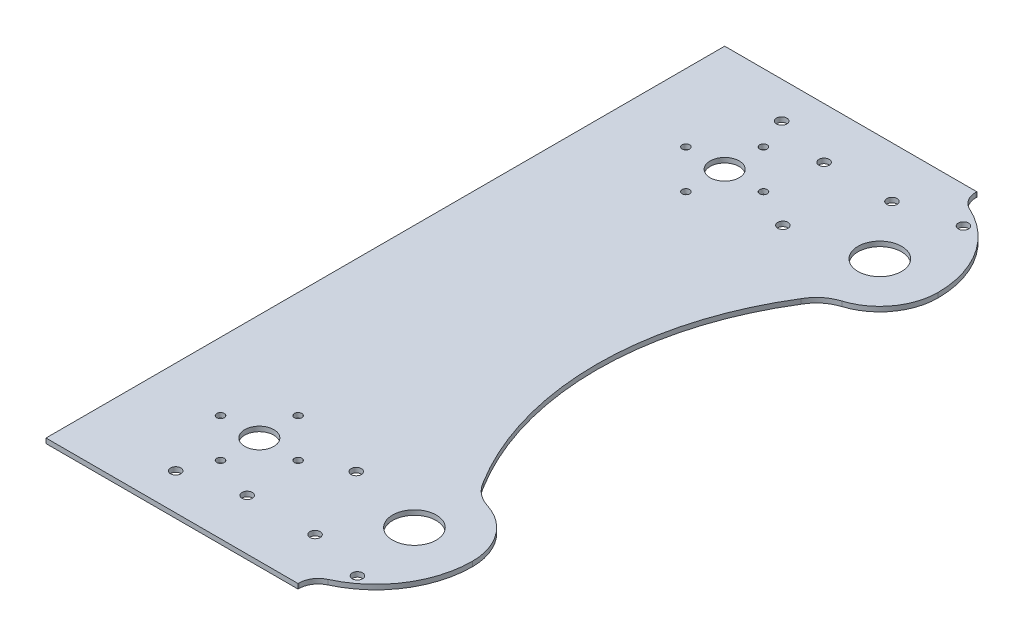
SolidWorks part; units mm, degrees
material "6061-T6 (SS)"
ref_plane "Front Plane" through (0, 0, 0) normal (0, 0, 1) x (1, 0, 0)
ref_plane "Top Plane" through (0, 0, 0) normal (0, 1, 0) x (1, 0, 0)
ref_plane "Right Plane" through (0, 0, 0) normal (1, 0, 0) x (0, 0, -1)
sketch "Sketch1" plane through (0, 0, 0) normal (0, 1, 0) x (1, 0, 0)
  line L1 (82.55, -222.25) -> (-82.55, -222.25)
  line L2 (82.55, -222.25) -> (82.55, 222.25)
  line L3 (82.55, 222.25) -> (-82.55, 222.25)
  line L4 (-82.55, -222.25) -> (-82.55, 222.25)
  line L5 (82.55, -222.25) -> (-82.55, 222.25) construction
  line L6 (82.55, 222.25) -> (-82.55, -222.25) construction
  point P0 (0, 0)
  dimension "D1" = 165.1
  dimension "D2" = 444.5
extrude "Boss-Extrude1" add sketch "Sketch1" along normal blind 3.175
sketch "Sketch3" plane through (0, 3.175, 0) normal (0, 1, 0) x (1, 0, 0)
  arc A0 (-3.175, -152.4) -> (-22.225, -152.4) centre (-12.7, -152.4) ccw construction
  arc A1 (-22.225, -152.4) -> (-3.175, -152.4) centre (-12.7, -152.4) ccw construction
  arc A2 (-3.175, -152.4) -> (-22.225, -152.4) centre (-12.7, -152.4) ccw
  arc A3 (-22.225, -152.4) -> (-3.175, -152.4) centre (-12.7, -152.4) ccw
  arc A4 (-3.175, 152.4) -> (-22.225, 152.4) centre (-12.7, 152.4) ccw construction
  arc A5 (-22.225, 152.4) -> (-3.175, 152.4) centre (-12.7, 152.4) ccw construction
  arc A6 (-3.175, 152.4) -> (-22.225, 152.4) centre (-12.7, 152.4) ccw
  arc A7 (-22.225, 152.4) -> (-3.175, 152.4) centre (-12.7, 152.4) ccw
extrude "Cut-Extrude2" cut sketch "Sketch3" against normal through all
hole_wizard "#10 (0.1935) Diameter Hole1" positions "Sketch4" profile "Sketch5" hole size "#10" standard "ANSI Inch" end condition through all
sketch "Sketch4" plane through (0, 3.175, 0) normal (0, 1, 0) x (1, 0, 0)
  arc A0 (-10.6807, -127) -> (-14.7193, -127) centre (-12.7, -127) ccw construction
  arc A1 (-14.7193, -127) -> (-10.6807, -127) centre (-12.7, -127) ccw construction
  arc A2 (-36.0807, -152.4) -> (-40.1193, -152.4) centre (-38.1, -152.4) ccw construction
  arc A3 (-40.1193, -152.4) -> (-36.0807, -152.4) centre (-38.1, -152.4) ccw construction
  arc A4 (-10.6807, -177.8) -> (-14.7193, -177.8) centre (-12.7, -177.8) ccw construction
  arc A5 (-14.7193, -177.8) -> (-10.6807, -177.8) centre (-12.7, -177.8) ccw construction
  arc A6 (14.7193, -152.4) -> (10.6807, -152.4) centre (12.7, -152.4) ccw construction
  arc A7 (10.6807, -152.4) -> (14.7193, -152.4) centre (12.7, -152.4) ccw construction
  arc A8 (-10.6807, -127) -> (-14.7193, -127) centre (-12.7, -127) ccw construction
  arc A9 (-14.7193, -127) -> (-10.6807, -127) centre (-12.7, -127) ccw construction
  arc A10 (-36.0807, -152.4) -> (-40.1193, -152.4) centre (-38.1, -152.4) ccw construction
  arc A11 (-40.1193, -152.4) -> (-36.0807, -152.4) centre (-38.1, -152.4) ccw construction
  arc A12 (-10.6807, -177.8) -> (-14.7193, -177.8) centre (-12.7, -177.8) ccw construction
  arc A13 (-14.7193, -177.8) -> (-10.6807, -177.8) centre (-12.7, -177.8) ccw construction
  arc A14 (14.7193, -152.4) -> (10.6807, -152.4) centre (12.7, -152.4) ccw construction
  arc A15 (10.6807, -152.4) -> (14.7193, -152.4) centre (12.7, -152.4) ccw construction
  arc A16 (14.7193, 152.4) -> (10.6807, 152.4) centre (12.7, 152.4) ccw construction
  arc A17 (10.6807, 152.4) -> (14.7193, 152.4) centre (12.7, 152.4) ccw construction
  arc A18 (-10.6807, 177.8) -> (-14.7193, 177.8) centre (-12.7, 177.8) ccw construction
  arc A19 (-14.7193, 177.8) -> (-10.6807, 177.8) centre (-12.7, 177.8) ccw construction
  arc A20 (-36.0807, 152.4) -> (-40.1193, 152.4) centre (-38.1, 152.4) ccw construction
  arc A21 (-40.1193, 152.4) -> (-36.0807, 152.4) centre (-38.1, 152.4) ccw construction
  arc A22 (-10.6807, 127) -> (-14.7193, 127) centre (-12.7, 127) ccw construction
  arc A23 (-14.7193, 127) -> (-10.6807, 127) centre (-12.7, 127) ccw construction
  arc A24 (14.7193, 152.4) -> (10.6807, 152.4) centre (12.7, 152.4) ccw
  arc A25 (10.6807, 152.4) -> (14.7193, 152.4) centre (12.7, 152.4) ccw
  arc A26 (-10.6807, 177.8) -> (-14.7193, 177.8) centre (-12.7, 177.8) ccw
  arc A27 (-14.7193, 177.8) -> (-10.6807, 177.8) centre (-12.7, 177.8) ccw
  arc A28 (-36.0807, 152.4) -> (-40.1193, 152.4) centre (-38.1, 152.4) ccw
  arc A29 (-40.1193, 152.4) -> (-36.0807, 152.4) centre (-38.1, 152.4) ccw
  arc A30 (-10.6807, 127) -> (-14.7193, 127) centre (-12.7, 127) ccw
  arc A31 (-14.7193, 127) -> (-10.6807, 127) centre (-12.7, 127) ccw
  point P0 (-12.7, -177.8)
  point P2 (-38.1, -152.4)
  point P4 (-12.7, -127)
  point P6 (12.7, -152.4)
  point P44 (-12.7, 177.8)
  point P50 (-38.1, 152.4)
  point P56 (-12.7, 127)
  point P68 (12.7, 152.4)
sketch "Sketch5" plane through (-12.7, 3.175, 177.8) normal (1, 0, 0) x (0, 0, 1)
  line L0 (0, 0) -> (0, 3.175)
  line L1 (0, 3.175) -> (2.4574, 3.175)
  line L2 (2.4574, 3.175) -> (2.4574, 0)
  line L5 (2.4574, 0) -> (0, 0)
  line L11 (0, -6.35) -> (0, 107.95) construction
  dimension "Thru Hole Dia." = 4.9149
  dimension "Thru Hole Depth" = 3.175
sketch "Sketch6" plane through (0, 3.175, 0) normal (0, 1, 0) x (1, 0, 0)
  line L0 (-12.7, -114.3) -> (-12.7, 114.3) construction
  line L1 (88.9, -152.4) -> (-12.7, -152.4) construction
  line L2 (88.9, 152.4) -> (-12.7, 152.4) construction
  line L3 (88.9, 152.4) -> (82.55, 152.4) construction
  line L4 (82.55, -222.25) -> (82.55, 222.25) construction
  circle A0 centre (-12.7, -152.4) radius 38.1 construction
  circle A1 centre (-12.7, 152.4) radius 38.1 construction
  circle A2 centre (88.9, -152.4) radius 38.1 construction
  circle A3 centre (88.9, 152.4) radius 38.1 construction
  dimension "D1" = 76.2
  dimension "D2" = 228.6
  dimension "D3" = 101.6
  dimension "D4" = 6.35
sketch "Sketch9" plane through (0, 0, 0) normal (0, 1, 0) x (1, 0, 0)
  line L0 (82.55, 222.25) -> (82.55, 212.9751)
  line L1 (82.55, -222.25) -> (82.55, 222.25) construction
  line L2 (82.55, 91.8249) -> (82.55, 82.55)
  line L3 (82.55, 222.25) -> (80.9625, 222.25)
  line L4 (82.55, 222.25) -> (-82.55, 222.25) construction
  line L5 (80.9625, 222.25) -> (80.9625, 82.55)
  line L6 (80.9625, 82.55) -> (82.55, 82.55)
  line L7 (0, 0) -> (145.4468, 0) construction
  line L8 (80.9625, -222.25) -> (80.9625, -82.55)
  line L9 (80.9625, -82.55) -> (82.55, -82.55)
  line L10 (82.55, -82.55) -> (82.55, -91.8249)
  line L11 (82.55, -212.9751) -> (82.55, -222.25)
  line L12 (82.55, -222.25) -> (80.9625, -222.25)
  line L13 (-82.55, -222.25) -> (82.55, -222.25) construction
  arc A0 (100.33, 116.0549) -> (127, 152.4) centre (88.9, 152.4) ccw
  arc A1 (100.33, 116.0549) -> (82.55, 91.8249) centre (107.95, 91.8249) ccw
  arc A3 (127, -152.4) -> (100.33, -116.0549) centre (88.9, -152.4) ccw
  arc A5 (82.55, -91.8249) -> (100.33, -116.0549) centre (107.95, -91.8249) ccw
  circle A6 centre (88.9, 152.4) radius 38.1 construction
  arc A8 (127, -152.4) -> (82.55, -212.9751) centre (63.5, -152.4) cw
  arc A10 (127, 152.4) -> (82.55, 212.9751) centre (63.5, 152.4) ccw
  point P8 (82.55, -213.1942)
  point P15 (82.55, 114.8329)
  point P23 (0, 0)
  dimension "D1" = 25.4
  dimension "D4" = 139.7
  dimension "D5" = 38.1
  dimension "D2" = 25.4
  dimension "D3" = 1.5875
extrude "Boss-Extrude2" add sketch "Sketch9" along normal blind 3.175
fillet "Fillet1" radius 12.7 2 edges at (82.55, 1.5875, 212.9751) (82.55, 1.5875, -212.9751)
sketch "Sketch7" plane through (0, 3.175, 0) normal (0, 1, 0) x (1, 0, 0)
  circle A0 centre (88.9, -152.4) radius 14.2875
  circle A1 centre (88.9, 152.4) radius 14.2875
  dimension "D1" = 28.575
extrude "Cut-Extrude3" cut sketch "Sketch7" against normal through all
sketch "Sketch8" plane through (0, 3.175, 0) normal (0, 1, 0) x (1, 0, 0)
  line L0 (87.4719, 106.8517) -> (87.4719, -106.8517)
  arc A1 (87.4719, 106.8517) -> (87.4719, -106.8517) centre (252.7977, 0) ccw
  arc A4 (82.55, -91.8249) -> (100.33, -116.0549) centre (107.95, -91.8249) ccw construction
  arc A5 (100.33, 116.0549) -> (82.55, 91.8249) centre (107.95, 91.8249) ccw construction
  dimension "D1" = 196.85
extrude "Cut-Extrude4" cut sketch "Sketch8" against normal through all
sketch "Sketch10" plane through (0, 3.175, 0) normal (0, 1, 0) x (1, 0, 0)
  circle A0 centre (38.1, -139.7) radius 3.3782 construction
  circle A1 centre (-21.4312, -198.4375) radius 3.3782 construction
  circle A2 centre (15.875, -188.9125) radius 3.3782 construction
  circle A3 centre (60.325, -188.9125) radius 3.3782 construction
  circle A4 centre (97.6313, -198.4375) radius 3.3782 construction
  circle A5 centre (38.1, -139.7) radius 3.3782
  circle A6 centre (-21.4312, -198.4375) radius 3.3782
  circle A7 centre (15.875, -188.9125) radius 3.3782
  circle A8 centre (60.325, -188.9125) radius 3.3782
  circle A9 centre (97.6313, -198.4375) radius 3.3782
  circle A10 centre (97.6313, 198.4375) radius 3.3782 construction
  circle A11 centre (60.325, 188.9125) radius 3.3782 construction
  circle A12 centre (15.875, 188.9125) radius 3.3782 construction
  circle A13 centre (38.1, 139.7) radius 3.3782 construction
  circle A14 centre (-21.4312, 198.4375) radius 3.3782 construction
  circle A15 centre (97.6313, 198.4375) radius 3.3782
  circle A16 centre (60.325, 188.9125) radius 3.3782
  circle A17 centre (15.875, 188.9125) radius 3.3782
  circle A18 centre (38.1, 139.7) radius 3.3782
  circle A19 centre (-21.4312, 198.4375) radius 3.3782
extrude "Cut-Extrude5" cut sketch "Sketch10" against normal through all
